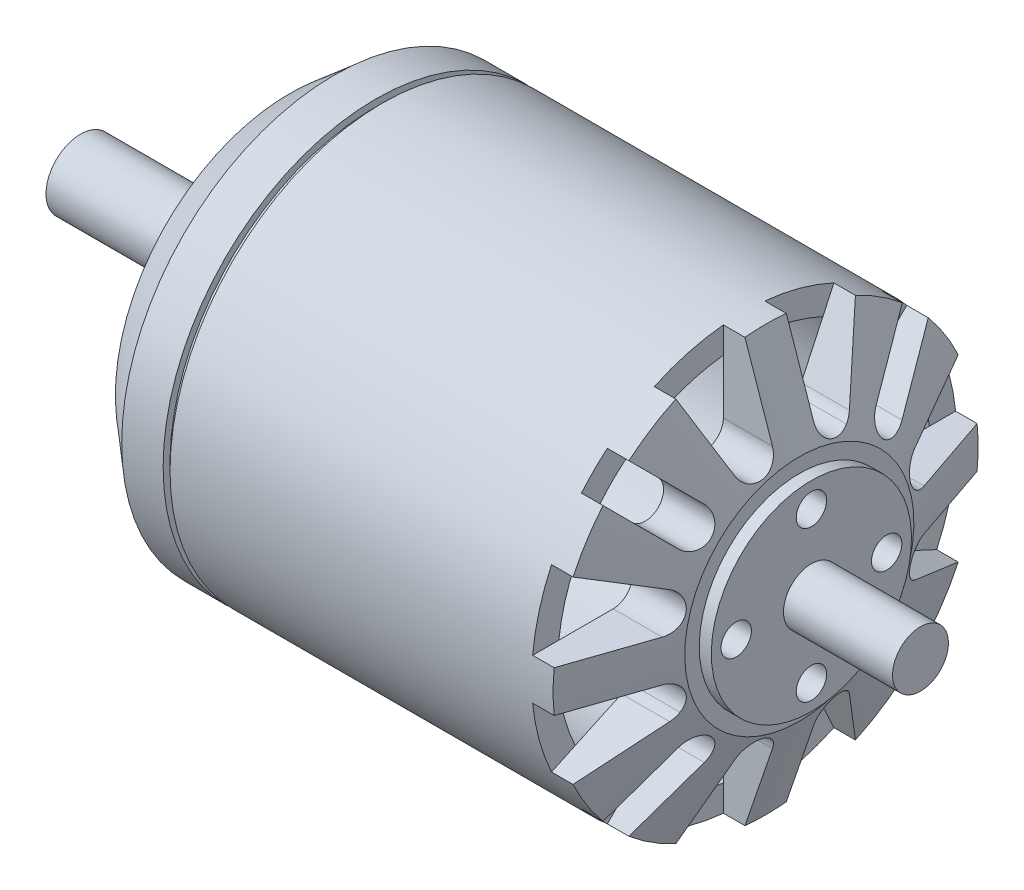
SolidWorks part; units mm, degrees
ref_plane "Alzado" through (0, 0, 0) normal (0, 0, 1) x (1, 0, 0)
ref_plane "Planta" through (0, 0, 0) normal (0, 1, 0) x (1, 0, 0)
ref_plane "Vista lateral" through (0, 0, 0) normal (1, 0, 0) x (0, 0, -1)
sketch "Croquis1" plane through (0, 0, 0) normal (0, 0, 1) x (1, 0, 0)
  line L0 (-68.0028, 0) -> (68.0028, 0) construction
  line L1 (-68.0028, 0) -> (-68.0028, 5)
  line L2 (-68.0028, 5) -> (-37.7028, 5)
  line L3 (-37.7028, 5) -> (-37.7028, 25.25)
  line L4 (-37.7028, 25.25) -> (-31.25, 30.7828)
  line L5 (-31.25, 30.7828) -> (-25.25, 30.7828)
  line L6 (-25.25, 30.7828) -> (-25.25, 29.7828)
  line L7 (-25.25, 29.7828) -> (-24.25, 29.7828)
  line L8 (-24.25, 29.7828) -> (-24.25, 30.7828)
  line L9 (-24.25, 30.7828) -> (31.25, 30.7828)
  line L10 (36.1335, 14.5) -> (36.1335, 16.6)
  line L11 (36.1335, 14.5) -> (37.8835, 14.5)
  line L12 (37.8835, 14.5) -> (37.8835, 4.05)
  line L13 (37.8835, 4.05) -> (53.6835, 4.05)
  line L14 (53.6835, 4.05) -> (53.6835, 0)
  line L15 (36.1335, 16.6) -> (31.25, 30.7828)
  line L16 (0, 0) -> (0, 30.7828) construction
  line L17 (-68.0028, 0) -> (53.6835, 0)
  point P4 (0, 0)
  point P15 (53.6835, 2.025)
  dimension "D1" = 8.1
  dimension "D2" = 15.8
  dimension "D3" = 29
  dimension "D4" = 1.75
  dimension "D5" = 33.2
  dimension "D6" = 15
  dimension "D7" = 19
  dimension "D8" = 31.25
  dimension "D9" = 62.5
  dimension "D10" = 1
  dimension "D11" = 6
  dimension "D12" = 10
  dimension "D13" = 30.3
  dimension "D14" = 50.5
  dimension "D15" = 8.5
revolve "Revolución1" add sketch "Croquis1" angle 360 about L0
sketch "Croquis2" plane through (37.8835, 0, 0) normal (1, 0, 0) x (0, 0, -1)
  line L0 (0, -14.5) -> (0, 14.5) construction
  line L1 (-14.5, 0) -> (14.5, 0) construction
  circle A0 centre (0, 0) radius 14.5 construction
  circle A1 centre (0, 0) radius 14.5 construction
  circle A2 centre (0, 10.9) radius 2.2
  circle A3 centre (10.9, 0) radius 2.2
  circle A4 centre (0, -10.9) radius 2.2
  circle A5 centre (-10.9, 0) radius 2.2
  point P8 (0, 0)
  point P13 (0, 0)
  point P17 (0, 13.1)
  point P18 (13.1, 0)
  dimension "D3" = 4.4
  dimension "D1" = 1.4
  dimension "D2" = 1.4
extrude "Cortar-Extruir1" cut sketch "Croquis2" against normal blind 14
sketch "Croquis3" plane through (36.1335, 0, 0) normal (1, 0, 0) x (0, 0, -1)
  line L0 (-30.7828, 0) -> (30.7828, 0) construction
  line L1 (0, -30.7828) -> (0, 30.7828) construction
  line L2 (3, 30.6362) -> (3, 18.971)
  line L3 (0, 0) -> (13.0094, 27.8987) construction
  line L4 (13.0094, 27.8987) -> (8.2819, 17.7606)
  line L5 (0, 0) -> (8.1209, 29.6923) construction
  line L6 (0, 0) -> (21.7667, 21.7667) construction
  line L7 (19.8121, 23.5597) -> (12.4451, 16.1927)
  line L8 (16.1927, 12.4451) -> (23.5597, 19.8121)
  line L9 (30.6362, 3) -> (18.971, 3)
  line L10 (27.8987, 13.0094) -> (17.7606, 8.2819)
  line L11 (-30.6362, 3) -> (-18.971, 3)
  line L12 (-27.8987, 13.0094) -> (-17.7606, 8.2819)
  line L13 (-16.1927, 12.4451) -> (-23.5597, 19.8121)
  line L14 (-19.8121, 23.5597) -> (-12.4451, 16.1927)
  line L15 (-13.0094, 27.8987) -> (-8.2819, 17.7606)
  line L16 (-3, 30.6362) -> (-3, 18.971)
  line L17 (-3, -30.6362) -> (-3, -18.971)
  line L18 (-13.0094, -27.8987) -> (-8.2819, -17.7606)
  line L19 (-19.8121, -23.5597) -> (-12.4451, -16.1927)
  line L20 (-16.1927, -12.4451) -> (-23.5597, -19.8121)
  line L21 (-27.8987, -13.0094) -> (-17.7606, -8.2819)
  line L22 (-30.6362, -3) -> (-18.971, -3)
  line L23 (27.8987, -13.0094) -> (17.7606, -8.2819)
  line L24 (30.6362, -3) -> (18.971, -3)
  line L25 (16.1927, -12.4451) -> (23.5597, -19.8121)
  line L26 (19.8121, -23.5597) -> (12.4451, -16.1927)
  line L27 (13.0094, -27.8987) -> (8.2819, -17.7606)
  line L28 (3, -30.6362) -> (3, -18.971)
  circle A0 centre (0, 0) radius 30.7828 construction
  circle A1 centre (0, 0) radius 30.7828 construction
  arc A2 (3, 18.971) -> (7.4049, 16.7051) centre (5.7853, 18.971) ccw
  arc A3 (3, 30.6362) -> (13.0094, 27.8987) centre (0, 0) cw
  circle A4 centre (0, 0) radius 16.6 construction
  arc A5 (8.2819, 17.7606) -> (7.4049, 16.7051) centre (5.8349, 18.9016) cw
  arc A6 (12.4451, 16.1927) -> (16.1927, 12.4451) centre (14.3189, 14.3189) ccw
  arc A7 (19.8121, 23.5597) -> (23.5597, 19.8121) centre (0, 0) cw
  arc A8 (17.7606, 8.2819) -> (16.7051, 7.4049) centre (18.9016, 5.8349) ccw
  arc A9 (18.971, 3) -> (16.7051, 7.4049) centre (18.971, 5.7853) cw
  arc A10 (30.6362, 3) -> (27.8987, 13.0094) centre (0, 0) ccw
  arc A11 (-19.8121, 23.5597) -> (-23.5597, 19.8121) centre (0, 0) ccw
  arc A12 (-30.6362, 3) -> (-27.8987, 13.0094) centre (0, 0) cw
  arc A13 (-18.971, 3) -> (-16.7051, 7.4049) centre (-18.971, 5.7853) ccw
  arc A14 (-17.7606, 8.2819) -> (-16.7051, 7.4049) centre (-18.9016, 5.8349) cw
  arc A15 (-12.4451, 16.1927) -> (-16.1927, 12.4451) centre (-14.3189, 14.3189) cw
  arc A16 (-8.2819, 17.7606) -> (-7.4049, 16.7051) centre (-5.8349, 18.9016) ccw
  arc A17 (-3, 18.971) -> (-7.4049, 16.7051) centre (-5.7853, 18.971) cw
  arc A18 (-3, 30.6362) -> (-13.0094, 27.8987) centre (0, 0) ccw
  arc A19 (-3, -30.6362) -> (-13.0094, -27.8987) centre (0, 0) cw
  arc A20 (-3, -18.971) -> (-7.4049, -16.7051) centre (-5.7853, -18.971) ccw
  arc A21 (-8.2819, -17.7606) -> (-7.4049, -16.7051) centre (-5.8349, -18.9016) cw
  arc A22 (-12.4451, -16.1927) -> (-16.1927, -12.4451) centre (-14.3189, -14.3189) ccw
  arc A23 (-17.7606, -8.2819) -> (-16.7051, -7.4049) centre (-18.9016, -5.8349) ccw
  arc A24 (-18.971, -3) -> (-16.7051, -7.4049) centre (-18.971, -5.7853) cw
  arc A25 (-30.6362, -3) -> (-27.8987, -13.0094) centre (0, 0) ccw
  arc A26 (-19.8121, -23.5597) -> (-23.5597, -19.8121) centre (0, 0) cw
  arc A27 (30.6362, -3) -> (27.8987, -13.0094) centre (0, 0) cw
  arc A28 (18.971, -3) -> (16.7051, -7.4049) centre (18.971, -5.7853) ccw
  arc A29 (17.7606, -8.2819) -> (16.7051, -7.4049) centre (18.9016, -5.8349) cw
  arc A30 (19.8121, -23.5597) -> (23.5597, -19.8121) centre (0, 0) ccw
  arc A31 (12.4451, -16.1927) -> (16.1927, -12.4451) centre (14.3189, -14.3189) cw
  arc A32 (8.2819, -17.7606) -> (7.4049, -16.7051) centre (5.8349, -18.9016) ccw
  arc A33 (3, -30.6362) -> (13.0094, -27.8987) centre (0, 0) ccw
  arc A34 (3, -18.971) -> (7.4049, -16.7051) centre (5.7853, -18.971) cw
  point P6 (0, 0)
  point P12 (0, 0)
  point P16 (4.5112, 16.4942)
  point P21 (4.3793, 16.0119)
  point P24 (8.195, 17.5743)
  point P29 (12.4451, 12.4451)
  point P31 (11.738, 11.738)
  point P97 (11.738, -11.738)
  point P98 (12.4451, -12.4451)
  point P99 (8.195, -17.5743)
  point P100 (4.3793, -16.0119)
  point P101 (4.5112, -16.4942)
  dimension "D4" = 2.7
  dimension "D1" = 6
  dimension "D2" = 65
  dimension "D3" = 0.5
  dimension "D5" = 45
  dimension "D6" = 5.3
  dimension "D7" = 1
extrude "Cortar-Extruir2" cut sketch "Croquis3" against normal blind 8
sketch "Croquis4" plane through (28.1335, 0, 0) normal (1, 0, 0) x (0, 0, -1)
  circle A0 centre (0, 0) radius 27
  dimension "D1" = 54
extrude "Cortar-Extruir3" cut sketch "Croquis4" against normal up to surface (52.3835 mm away) up to face at (-24.25, -29.7828, 0)
